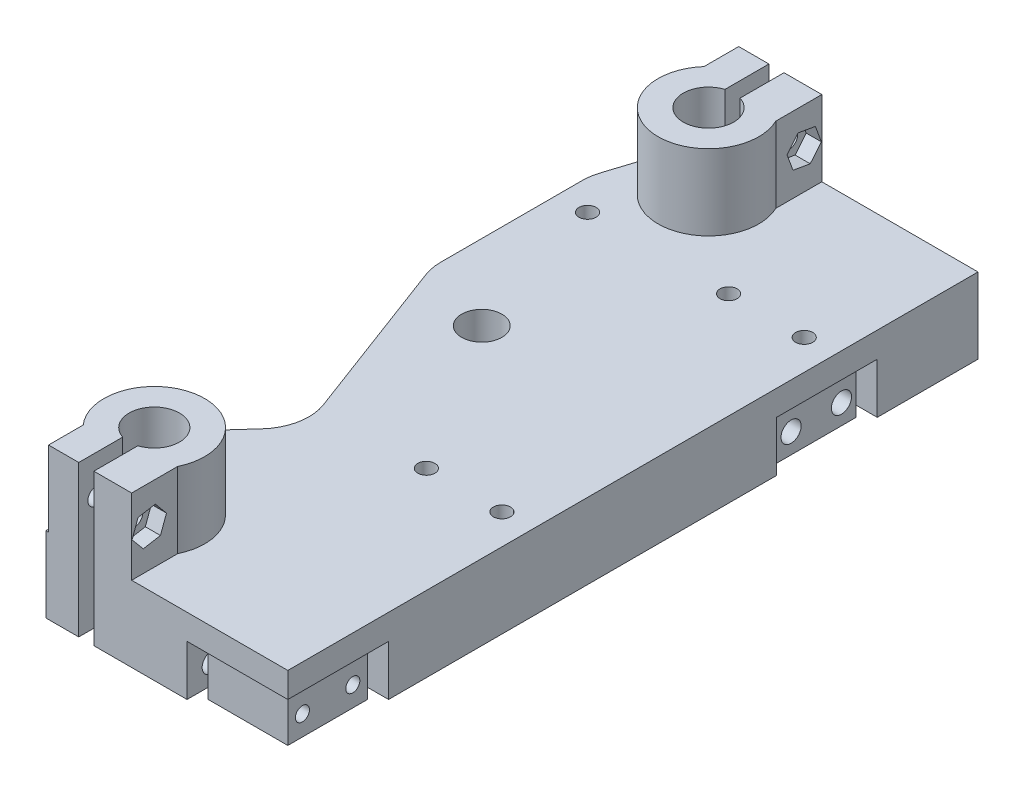
SolidWorks part; units mm, degrees
ref_plane "Płaszczyzna przednia" through (0, 0, 0) normal (0, 0, 1) x (1, 0, 0)
ref_plane "Płaszczyzna górna" through (0, 0, 0) normal (0, 1, 0) x (1, 0, 0)
ref_plane "Płaszczyzna prawa" through (0, 0, 0) normal (1, 0, 0) x (0, 0, -1)
sketch "Szkic1" plane through (0, 0, 0) normal (0, 1, 0) x (1, 0, 0)
  line L0 (-27.5, 36.5) -> (-20.5, 58.5)
  line L1 (27.5, -78.5) -> (-20.5, -78.5)
  line L2 (27.5, -78.5) -> (27.5, 58.5)
  line L3 (27.5, 58.5) -> (-20.5, 58.5)
  line L4 (-27.5, -36.5) -> (-27.5, 36.5)
  line L5 (27.5, 0) -> (-46.9742, 0) construction
  line L6 (-14, -69.7697) -> (-14, -78.5)
  line L7 (-27.5, -36.5) -> (-20.5, -78.5)
  line L8 (-11, -69.7697) -> (-11, -78.5)
  line L9 (-14, 49.7697) -> (-14, 58.5)
  line L10 (-11, 49.7697) -> (-11, 58.5)
  circle A0 centre (-21.5, 30) radius 1.7
  circle A1 centre (6.5, 30) radius 1.7
  circle A2 centre (21.5, 30) radius 1.7
  circle A3 centre (21.5, -30) radius 1.7
  circle A4 centre (6.5, -30) radius 1.7
  circle A5 centre (-21.5, -30) radius 1.7
  circle A6 centre (-12.5, -65) radius 5
  circle A7 centre (-12.5, 0) radius 4
  circle A8 centre (-12.5, 45) radius 5
  point P0 (0, 0)
  dimension "D7" = 6
  dimension "D10" = 3.4
  dimension "D11" = 30
  dimension "D12" = 15
  dimension "D13" = 8
  dimension "D16" = 10
  dimension "D1" = 55
  dimension "D2" = 137
  dimension "D3" = 27.5
  dimension "D4" = 58.5
  dimension "D5" = 48
  dimension "D6" = 73
  dimension "D8" = 28
  dimension "D9" = 15
  dimension "D14" = 13.5
  dimension "D15" = 15
  dimension "D17" = 3
  dimension "D18" = 40
  dimension "D19" = 13.5
  dimension "D20" = 3
extrude "Dodanie-wyciągnięcie1" add sketch "Szkic1" along normal blind 15 contours L2 L5 A7 L4 L7 L1 L6 A6 L8 A5 A3 A4 | L5 L2 L3 L10 A8 L9 L0 L4 A7 A0 A1 A2 region at (1.1717, 0, -28.2799) region at (1.31, 0, 37.8952)
sketch "Szkic2" plane through (0, 15, 0) normal (0, 1, 0) x (1, 0, 0)
  line L0 (-11, -69.7697) -> (-11, -78.5) construction
  line L1 (-14, -69.7697) -> (-14, -78.5) construction
  line L2 (-11, -69.7697) -> (-11, -78.5)
  line L3 (-14, -69.7697) -> (-14, -78.5)
  line L4 (-20, -71.6144) -> (-20, -78.5)
  line L5 (-14, -78.5) -> (-20.5, -78.5) construction
  line L6 (-3.5, -69.3589) -> (-3.5, -78.5)
  line L7 (27.5, -78.5) -> (-11, -78.5) construction
  line L8 (-3.5, -78.5) -> (-11, -78.5)
  line L9 (-14, -78.5) -> (-20, -78.5)
  arc A0 (-11, -69.7697) -> (-14, -69.7697) centre (-12.5, -65) ccw construction
  arc A1 (-11, -69.7697) -> (-14, -69.7697) centre (-12.5, -65) ccw
  arc A2 (-3.5, -69.3589) -> (-20, -71.6144) centre (-12.5, -65) ccw
  dimension "D1" = 6
  dimension "D3" = 10
  dimension "D2" = 7.5
extrude "Dodanie-wyciągnięcie2" add sketch "Szkic2" along normal blind 15
sketch "Szkic3" plane through (-20, 0, 0) normal (-1, 0, 0) x (0, 0, 1)
  line L0 (71.6144, 30) -> (78.5, 30) construction
  line L1 (78.5, 30) -> (78.5, 15) construction
  circle A0 centre (75, 22.5) radius 1.7
  dimension "D1" = 7.5
  dimension "D3" = 3.4
  dimension "D2" = 3.5
extrude "Wytnij-wyciągnięcie1" cut sketch "Szkic3" against normal up to surface (16.5 mm away) up to face at (-3.5, 22.5, 73.9294)
sketch "Szkic4" plane through (-3.5, 0, 0) normal (1, 0, 0) x (0, 0, -1)
  line L1 (-71.5867, 23.0912) -> (-73.8054, 25.7516)
  line L2 (-73.8054, 25.7516) -> (-77.2186, 25.1604)
  line L3 (-77.2186, 25.1604) -> (-78.4133, 21.9088)
  line L4 (-78.5, 15) -> (-69.3589, 15)
  line L5 (-69.3589, 15) -> (-69.3589, 30)
  line L6 (-69.3589, 30) -> (-78.5, 30)
  line L7 (-78.5, 30) -> (-78.5, 15)
  line L8 (-78.5, 15) -> (-69.3589, 15)
  line L9 (-69.3589, 15) -> (-69.3589, 30)
  line L10 (-69.3589, 30) -> (-78.5, 30)
  line L11 (-78.5, 30) -> (-78.5, 15)
  line L12 (-78.4133, 21.9088) -> (-76.1946, 19.2484)
  line L13 (-76.1946, 19.2484) -> (-72.7814, 19.8396)
  line L14 (-72.7814, 19.8396) -> (-71.5867, 23.0912)
  circle A0 centre (-75, 22.5) radius 1.7 construction
  circle A1 centre (-75, 22.5) radius 1.7
  circle A2 centre (-75, 22.5) radius 3 construction
  circle M12 centre (-75, 22.5) radius 1.7
  dimension "D2" = 6
  dimension "D1" = 0
extrude "Wytnij-wyciągnięcie2" cut sketch "Szkic4" against normal blind 3 contours L13 L14 L1 L2 L3 L12 M12 region at (-3.5, 21.4979, 72.2725)
ref_plane "Płaszczyzna1" through (0, 0, 10) normal (0, 0, 1) x (1, 0, 0)
mirror "Lustro1" about plane through (0, 0, 10) normal (0, 0, 1) of "Dodanie-wyciągnięcie2", "Wytnij-wyciągnięcie2", "Wytnij-wyciągnięcie1"
sketch "Szkic5" plane through (0, 0, 0) normal (0, -1, 0) x (1, 0, 0)
  line L0 (27.5, -58.5) -> (-11, -58.5) construction
  line L1 (27.5, 78.5) -> (7.5, 78.5)
  line L2 (27.5, 78.5) -> (27.5, 58.5)
  line L3 (27.5, 58.5) -> (7.5, 58.5)
  line L4 (7.5, 78.5) -> (7.5, 58.5)
  line L5 (27.5, -38.5) -> (7.5, -38.5)
  line L6 (27.5, -38.5) -> (27.5, -18.5)
  line L7 (27.5, -18.5) -> (7.5, -18.5)
  line L8 (7.5, -38.5) -> (7.5, -18.5)
  line L9 (27.5, 78.5) -> (27.5, -58.5) construction
  dimension "D1" = 20
  dimension "D2" = 20
  dimension "D3" = 20
extrude "Wytnij-wyciągnięcie3" cut sketch "Szkic5" against normal blind 10
sketch "Szkic9" plane through (0, 10, 0) normal (0, -1, 0) x (1, 0, 0)
  line L0 (27.5, 58.5) -> (27.5, 78.5) construction
  line L1 (25.4, 76.4) -> (9.6, 76.4)
  line L2 (25.4, 76.4) -> (25.4, 60.6)
  line L3 (25.4, 60.6) -> (9.6, 60.6)
  line L4 (9.6, 76.4) -> (9.6, 60.6)
  line L5 (27.5, 78.5) -> (7.5, 78.5) construction
  line L12 (9.6, -36.4) -> (9.6, -20.6)
  line L13 (25.4, -20.6) -> (9.6, -20.6)
  line L14 (25.4, -36.4) -> (25.4, -20.6)
  line L15 (25.4, -36.4) -> (9.6, -36.4)
  line L16 (27.5, -58.5) -> (-11, -58.5) construction
  dimension "D1" = 2.1
  dimension "D2" = 2.1
  dimension "D3" = 15.8
  dimension "D4" = 22.1
extrude "Dodanie-wyciągnięcie3" add sketch "Szkic9" along normal blind 10
sketch "Szkic6" plane through (7.5, 0, 0) normal (1, 0, 0) x (0, 0, -1)
  line L0 (-78.5, 0) -> (-58.5, 0) construction
  line L1 (-78.5, 10) -> (-78.5, 0) construction
  line L2 (58.5, 10) -> (58.5, 0) construction
  circle A0 centre (-73.5, 4) radius 2
  circle A1 centre (33.5, 4) radius 2
  circle A2 centre (-63.5, 4) radius 2
  circle A3 centre (23.5, 4) radius 2
  dimension "D1" = 4
  dimension "D3" = 4
  dimension "D5" = 10
  dimension "D2" = 5
  dimension "D4" = 25
  dimension "D6" = 10
extrude "Wytnij-wyciągnięcie4" cut sketch "Szkic6" against normal blind 8 and the other way through all
sketch "Szkic10" plane through (25.4, 0, 0) normal (1, 0, 0) x (0, 0, -1)
  line L0 (-76.5, 2.2679) -> (-76.5, -2.8728)
  line L1 (-73.5, 7.4641) -> (-76.5, 5.7321)
  line L2 (-76.5, 5.7321) -> (-76.5, 2.2679)
  line L3 (-76.5, 2.2679) -> (-73.5, 0.5359)
  line L4 (-73.5, 0.5359) -> (-70.5, 2.2679)
  line L5 (-70.5, 2.2679) -> (-70.5, 5.7321)
  line L6 (-70.5, 5.7321) -> (-73.5, 7.4641)
  line L7 (-63.5, 7.4641) -> (-66.5, 5.7321)
  line L8 (-66.5, 5.7321) -> (-66.5, 2.2679)
  line L9 (-66.5, 2.2679) -> (-63.5, 0.5359)
  line L10 (-63.5, 0.5359) -> (-60.5, 2.2679)
  line L11 (-60.5, 2.2679) -> (-60.5, 5.7321)
  line L12 (-60.5, 5.7321) -> (-63.5, 7.4641)
  line L13 (-76.5, -2.8728) -> (-70.5, -2.8728)
  line L14 (-70.5, -2.8728) -> (-70.5, 2.2679)
  line L15 (-66.5, 2.2679) -> (-66.5, -2.8728)
  line L16 (-66.5, -2.8728) -> (-60.5, -2.8728)
  line L17 (-60.5, -2.8728) -> (-60.5, 2.2679)
  circle A0 centre (-73.5, 4) radius 3 construction
  circle A1 centre (-63.5, 4) radius 3 construction
  circle M1 centre (-73.5, 4) radius 2
  circle M2 centre (-63.5, 4) radius 2
  line M4 (-76.4, 10) -> (-76.4, 0)
  line M5 (-76.4, 0) -> (-60.6, 0)
  line M6 (-60.6, 0) -> (-60.6, 10)
  dimension "D1" = 6
extrude "Wytnij-wyciągnięcie5" cut sketch "Szkic10" against normal blind 3.2 from offset 22 contours L5 L6 L1 L3 L4 M4 M1 | L13 L14 L3 L0 M5 M4 | L12 L7 L8 L9 L10 M6 M2 | L16 L17 L10 L15 M6 M5 | L9 L15 L10 M5 M6 | L14 L4 L3 M5 M4 region at (25.4, -1.4036, 73.5378) region at (25.4, 1.134, 66.4368) region at (25.4, -1.4036, 63.4622) region at (25.4, 4, 76.309) region at (25.4, 1.3183, 74.9816) region at (25.4, 4, 66.409) offset against normal yes
sketch "Szkic11" plane through (25.4, 0, 0) normal (1, 0, 0) x (0, 0, -1)
  circle A0 centre (-63.5, 4) radius 2 construction
  circle A1 centre (-73.5, 4) radius 2 construction
  circle A2 centre (-63.5, 4) radius 2
  circle A3 centre (-73.5, 4) radius 2
  circle A4 centre (-73.5, 4) radius 1.4
  circle A5 centre (-63.5, 4) radius 1.4
  dimension "D1" = 0.6
extrude "Dodanie-wyciągnięcie4" add sketch "Szkic11" against normal blind 15.8
mirror "Lustro2" about plane through (0, 0, 10) normal (0, 0, 1) of "Dodanie-wyciągnięcie4", "Wytnij-wyciągnięcie5"
sketch "Szkic12" plane through (0, 15, 0) normal (0, 1, 0) x (1, 0, 0)
  line L0 (-27.5, 5) -> (-12.5, -35)
  line L1 (-27.5, -36.5) -> (-27.5, 36.5) construction
  line L2 (-12.5, -35) -> (-27.5, -35)
  line L3 (-27.5, -35) -> (-27.5, 5)
  line L4 (-12.5, -35) -> (-25.3766, -49.2404)
  line L5 (-27.5, -36.5) -> (-20.5, -78.5) construction
  line L6 (-25.3766, -49.2404) -> (-27.5, -36.5)
  line L7 (-27.5, -36.5) -> (-27.5, -35)
  circle A0 centre (-21.5, -30) radius 1.7 construction
  line M7 (-27.5, 36.5) -> (-27.5, -36.5)
  line M8 (-27.5, -36.5) -> (-20.5, -78.5)
  dimension "D1" = 40
  dimension "D2" = 5
  dimension "D3" = 15
extrude "Wytnij-wyciągnięcie6" cut sketch "Szkic12" along direction (0, 1, 0) on the side against the normal blind 15 contours L4 L2 M7 M8 | L3 L0 L2 region at (-21.8657, 15, 39.7542)
fillet "Zaokrąglenie1" radius 10 4 edges at (-27.5, 7.5, -36.5) (-25.3766, 7.5, 49.2404) (-12.5, 7.5, 35) (-27.5, 7.5, -5)
